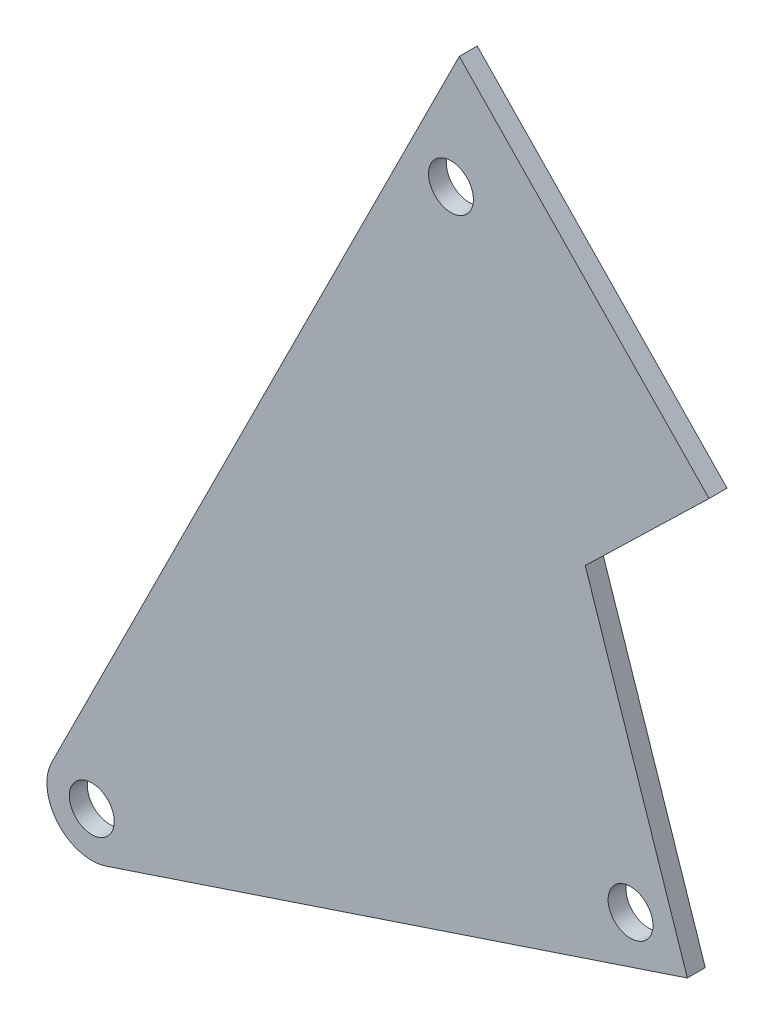
SolidWorks part; units mm, degrees
ref_plane "Front Plane" through (0, 0, 0) normal (0, 0, 1) x (1, 0, 0)
ref_plane "Top Plane" through (0, 0, 0) normal (0, 1, 0) x (1, 0, 0)
ref_plane "Right Plane" through (0, 0, 0) normal (1, 0, 0) x (0, 0, -1)
sketch "Sketch1" plane through (0, 0, 0) normal (0, 0, 1) x (1, 0, 0)
  line L0 (-76.2, 0) -> (0, 0) construction
  line L1 (0, 0) -> (0, 25.4) construction
  line L2 (0, 25.4) -> (0, 101.6) construction
  line L3 (0, 101.6) -> (-25.4, 101.6) construction
  line L4 (-24.2237, 118.1516) -> (-88.7355, -10.872)
  line L5 (-76.2, 0) -> (-25.4, 101.6) construction
  line L6 (-25.4, 101.6) -> (0, 25.4) construction
  line L7 (0, 25.4) -> (-76.2, 0) construction
  line L8 (-88.7355, -10.872) -> (8.0322, 21.3839)
  line L9 (8.0322, 21.3839) -> (-24.2237, 118.1516) construction
  line L10 (-24.2237, 118.1516) -> (11.1136, 81.6562)
  line L12 (11.1136, 81.6562) -> (-6.4045, 64.694)
  line L13 (-6.4045, 64.694) -> (8.0322, 21.3839)
  circle A0 centre (-76.2, 0) radius 3.175
  circle A1 centre (0, 25.4) radius 3.175
  circle A2 centre (-25.4, 101.6) radius 3.175
  dimension "D5" = 6.35
  dimension "D6" = 6.35
  dimension "D7" = 6.35
  dimension "D1" = 76.2
  dimension "D2" = 25.4
  dimension "D3" = 76.2
  dimension "D4" = 25.4
  dimension "D8" = 6.35
  dimension "D9" = 6.35
  dimension "D10" = 6.35
  dimension "D11" = 25.641
  dimension "D12" = 50.8
extrude "Boss-Extrude1" add sketch "Sketch1" along normal blind 2.54
fillet "Fillet1" radius 6.35 1 edges at (-88.7355, -10.872, 1.27)
